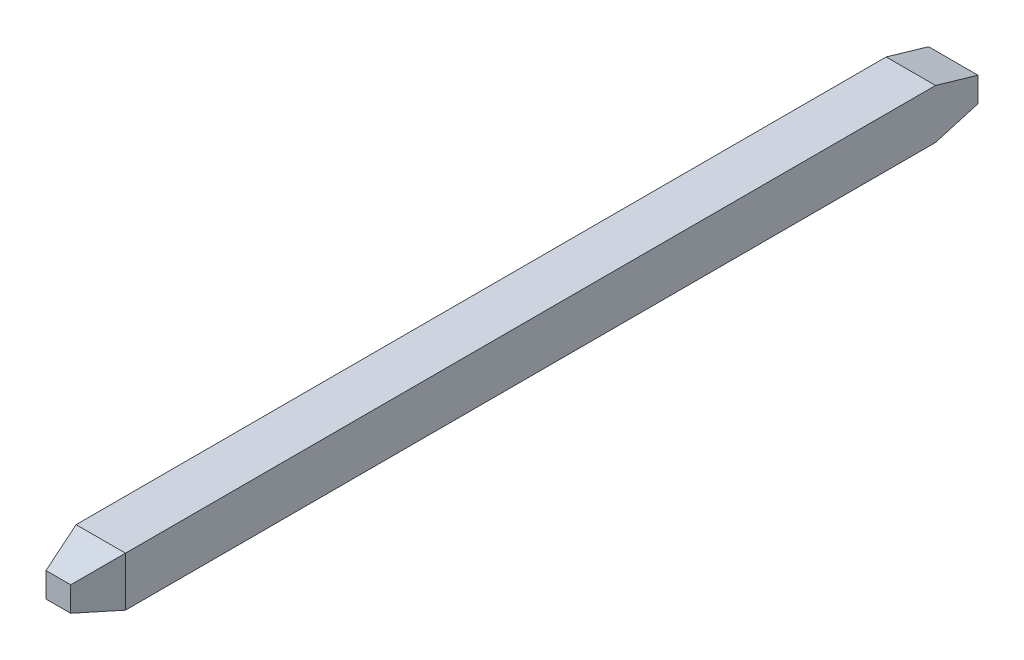
SolidWorks part; units mm, degrees
material "Латунь"
ref_plane "Спереди" through (0, 0, 0) normal (0, 0, 1) x (1, 0, 0)
ref_plane "Сверху" through (0, 0, 0) normal (0, 1, 0) x (1, 0, 0)
ref_plane "Справа" through (0, 0, 0) normal (1, 0, 0) x (0, 0, -1)
sketch "Эскиз1" plane through (0, 0, 0) normal (1, 0, 0) x (0, 0, -1)
  line L1 (-5.25, -0.32) -> (5.25, -0.32)
  line L2 (5.25, -0.32) -> (5.8, -0.16)
  line L3 (5.8, -0.16) -> (5.8, 0.16)
  line L4 (5.8, 0.16) -> (5.25, 0.32)
  line L5 (5.25, 0.32) -> (-5.25, 0.32)
  line L6 (-5.25, 0.32) -> (-5.8, 0.16)
  line L7 (-5.8, 0.16) -> (-5.8, -0.16)
  line L8 (-5.8, -0.16) -> (-5.25, -0.32)
  point P2 (-5.8, 0)
  point P11 (0, 0.32)
  dimension "D1" = 0.64
  dimension "D2" = 0.32
  dimension "D3" = 0.55
  dimension "D4" = 11.6
extrude "Бобышка-Вытянуть1" add sketch "Эскиз1" along normal blind 0.32 and the other way blind 0.32
sketch "Эскиз4" plane through (0, -0.32, 0) normal (0, -1, 0) x (1, 0, 0)
  line L0 (-0.32, 5.25) -> (-0.16, 5.8)
  line L1 (-0.32, 5.8) -> (0.32, 5.8) construction
  line L2 (-0.16, 5.8) -> (-0.32, 5.8)
  line L3 (-0.32, 5.8) -> (-0.32, 5.25)
  dimension "D1" = 0.16
extrude "Вырез-Вытянуть2" cut sketch "Эскиз4" against normal through all
mirror "Зеркальное отражение1" about plane through (0, 0, 0) normal (1, 0, 0) of "Вырез-Вытянуть2"
